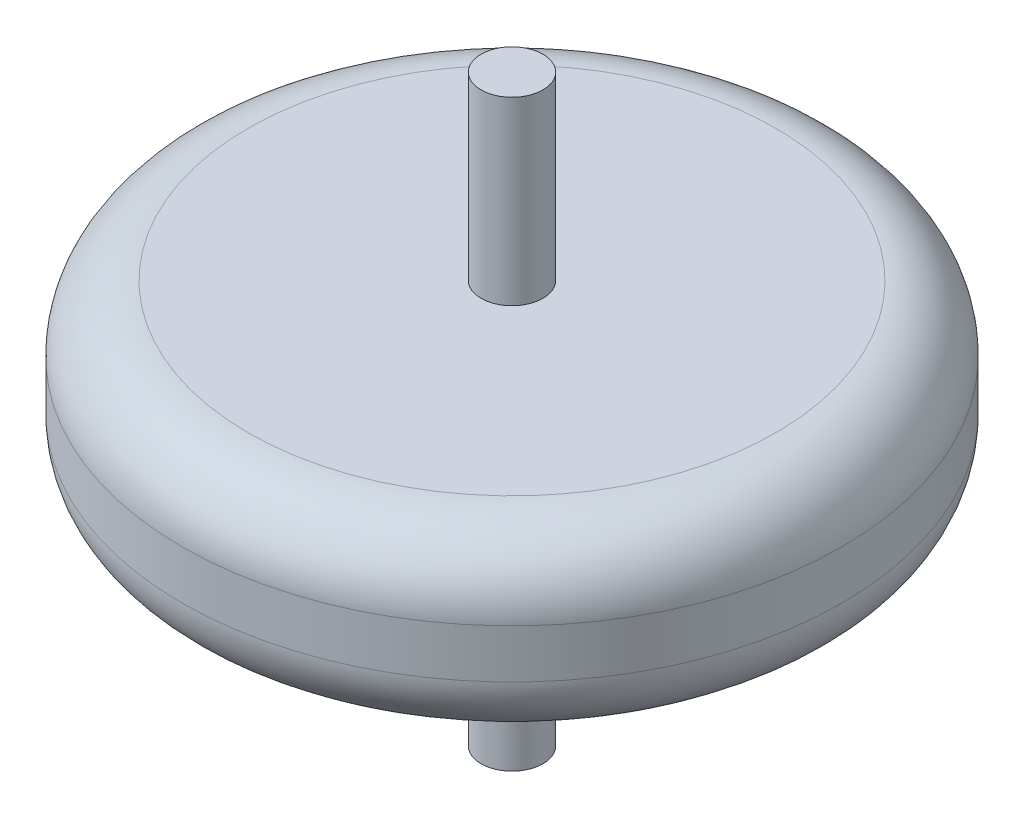
SolidWorks part; units mm, degrees
ref_plane "Front Plane" through (0, 0, 0) normal (0, 0, 1) x (1, 0, 0)
ref_plane "Top Plane" through (0, 0, 0) normal (0, 1, 0) x (1, 0, 0)
ref_plane "Right Plane" through (0, 0, 0) normal (1, 0, 0) x (0, 0, -1)
sketch "Sketch1" plane through (0, 0, 0) normal (0, 1, 0) x (1, 0, 0)
  circle A0 centre (0, 0) radius 101.6
  dimension "D1" = 203.2
extrude "Boss-Extrude1" add sketch "Sketch1" along normal blind 55.626
sketch "Sketch2" plane through (0, 55.626, 0) normal (0, 1, 0) x (1, 0, 0)
  circle A0 centre (0, 0) radius 9.525
  dimension "D1" = 19.05
extrude "Boss-Extrude2" add sketch "Sketch2" along normal blind 55.626 and the other way blind 124.206
fillet "Fillet1" radius 20.32 2 edges at (0, 0, 101.6) (0, 55.626, 101.6)
